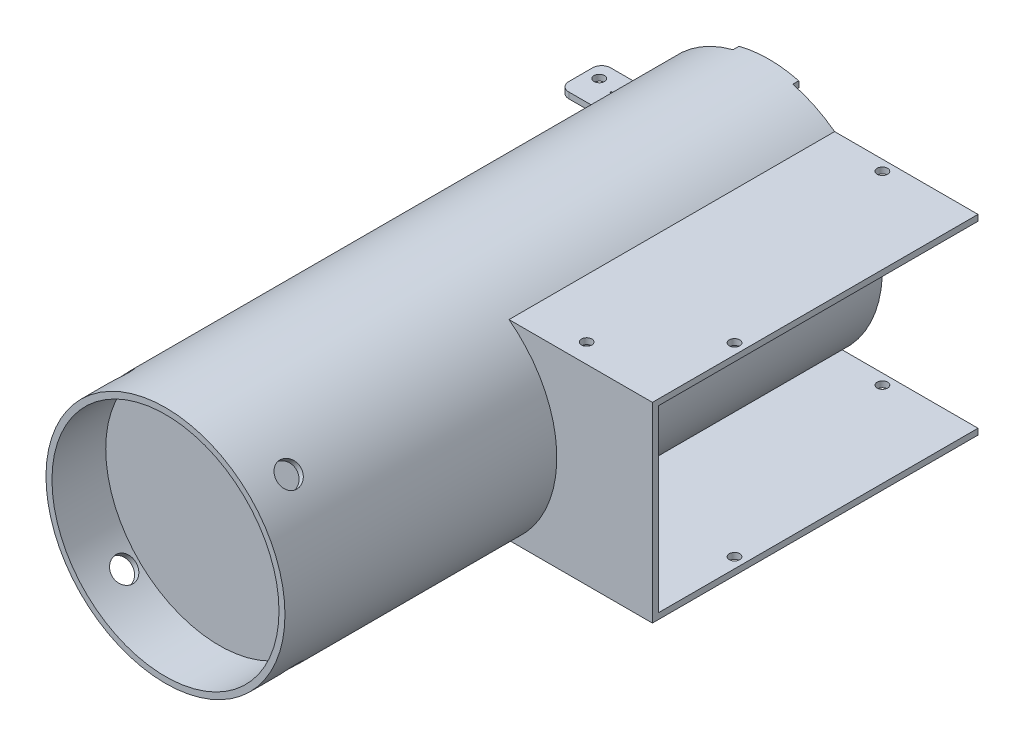
SolidWorks part; units mm, degrees
material "Acrylic (Medium-high impact)"
ref_plane "Front Plane" through (0, 0, 0) normal (0, 0, 1) x (1, 0, 0)
ref_plane "Top Plane" through (0, 0, 0) normal (0, 1, 0) x (1, 0, 0)
ref_plane "Right Plane" through (0, 0, 0) normal (1, 0, 0) x (0, 0, -1)
ref_axis "Axis1" through (0, 0, -12.1) along (0, 0, 1)
sketch "Sketch1" plane through (0, 0, 0) normal (0, 0, 1) x (1, 0, 0)
  circle A0 centre (0, 0) radius 38
  circle A1 centre (0, 0) radius 40
  dimension "D1" = 76
  dimension "D2" = 2
extrude "Boss-Extrude1" add sketch "Sketch1" along normal blind 200
ref_plane "Plane1" through (0, 0, 180) normal (0, 0, 1) x (1, 0, 0)
sketch "Sketch2" plane through (0, 0, 180) normal (0, 0, 1) x (1, 0, 0)
  circle A0 centre (0, 0) radius 40 construction
  circle A1 centre (0, 0) radius 40
extrude "Boss-Extrude2" add sketch "Sketch2" along normal blind 2
sketch "Sketch3" plane through (0, 0, 0) normal (0, 0, -1) x (-1, 0, 0)
  line L0 (-24, -32) -> (-72, -32)
  line L1 (-72, -32) -> (-72, -30)
  line L2 (-72, -30) -> (-26.4575, -30)
  line L3 (-24, 32) -> (-72, 32)
  line L4 (-72, 30) -> (-26.4575, 30)
  line L5 (-72, 32) -> (-72, 30)
  line L6 (-40, -15.2942) -> (-40, 13.2229) construction
  line L8 (0, 0) -> (-59.0266, 0) construction
  circle A1 centre (0, 0) radius 40 construction
  arc A2 (-24, 32) -> (-26.4575, 30) centre (0, 0) ccw
  arc A3 (-26.4575, -30) -> (-24, -32) centre (0, 0) ccw
  dimension "D1" = 60
  dimension "D2" = 2
  dimension "D3" = 32
extrude "Boss-Extrude3" add sketch "Sketch3" against normal blind 107
sketch "Sketch4" plane through (0, 0, 107) normal (0, 0, 1) x (1, 0, 0)
  line L2 (72, -32) -> (24, -32) construction
  line L3 (24, 32) -> (72, 32) construction
  line L4 (72, -32) -> (24, -32)
  line L5 (24, 32) -> (72, 32)
  line L6 (72, -32) -> (72, 32)
  circle A0 centre (0, 0) radius 40 construction
  arc A2 (24, -32) -> (24, 32) centre (0, 0) ccw
extrude "Boss-Extrude4" add sketch "Sketch4" along normal blind 2
sketch "Sketch5" plane through (0, 32, 0) normal (0, 1, 0) x (1, 0, 0)
  circle A5 centre (43.5, -102.5) radius 1.75 construction
  circle A6 centre (43.5, -102.5) radius 1.75
  circle A7 centre (43.5, -3.5) radius 1.75 construction
  circle A8 centre (43.5, -3.5) radius 1.75
  circle A9 centre (68.5, -78) radius 1.75 construction
  circle A10 centre (68.5, -78) radius 1.75
extrude "Cut-Extrude1" cut sketch "Sketch5" against normal through all
ref_plane "Plane2" through (0, 0, 0) normal (-0.7071, 0.7071, 0) x (0, 0, 1)
sketch "Sketch6" plane through (0, 0, 0) normal (-0.7071, 0.7071, 0) x (0, 0, 1)
  line L0 (200, -40) -> (200, 40) construction
  line L1 (200, -40) -> (200, 40) construction
  circle A0 centre (187, 0) radius 4
  dimension "D1" = 8
  dimension "D2" = 13
extrude "Cut-Extrude2" cut sketch "Sketch6" against normal up to next and the other way up to next
pattern_circular "CirPattern1" count 2 every 90 about axis through (0, 0, -12.1) along (0, 0, 1) of "Cut-Extrude2"
ref_plane "Plane3" through (-54, 0, 0) normal (1, 0, 0) x (0, 0, -1)
sketch "Sketch7" plane through (-54, 0, 0) normal (1, 0, 0) x (0, 0, -1)
  line L0 (0, 0) -> (-33.0452, 0) construction
  line L1 (-14, -11) -> (0, -11)
  line L2 (-14, -11) -> (-14, -13)
  line L3 (-14, -13) -> (0, -13)
  line L4 (0, -11) -> (0, -13)
  line L5 (0, -40) -> (0, 40) construction
  line L6 (0, 11) -> (0, 13)
  line L7 (-14, 13) -> (0, 13)
  line L8 (-14, 11) -> (-14, 13)
  line L9 (-14, 11) -> (0, 11)
  dimension "D1" = 2
  dimension "D2" = 14
  dimension "D3" = 22
extrude "Boss-Extrude5" add sketch "Sketch7" along normal up to surface (15.5422 mm away) up to face at (25.3934, 30.9059, 187.8976)
sketch "Sketch8" plane through (0, -13, 0) normal (0, -1, 0) x (1, 0, 0)
  line L6 (-37.8286, 14) -> (-37.8286, 0) construction
  line L7 (-37.8286, 0) -> (-54, 0) construction
  circle A0 centre (-49.7703, 5.0088) radius 1.75
  dimension "D3" = 3.5
  dimension "D1" = 11.9417
  dimension "D2" = 5.0088
extrude "Cut-Extrude3" cut sketch "Sketch8" against normal up to surface (26 mm away) up to face at (-45.9143, 13, 7)
fillet "Fillet1" radius 3 4 edges at (-54, 12, 0) (-54, -12, 0) (-54, -12, 14) (-54, 12, 14)
sketch "Sketch9" plane through (0, 11, 0) normal (0, -1, 0) x (1, 0, 0)
  circle A0 centre (-43.7703, 7.0088) radius 0.25
  circle A1 centre (-49.7703, 5.0088) radius 1.75 construction
  dimension "D1" = 6
  dimension "D2" = 2
  dimension "D3" = 0.5
extrude "Cut-Extrude4" cut sketch "Sketch9" against normal up to next
sketch "Sketch10" plane through (0, 0, 0) normal (0, 0, -1) x (-1, 0, 0)
  line L0 (-10, 38.7298) -> (-10, 36.6606)
  line L2 (10, 38.7298) -> (10, 36.6606)
  line L3 (-10, -36.6606) -> (-10, -38.7298)
  line L4 (10, -36.6606) -> (10, -38.7298)
  line L5 (-10, 36.6606) -> (10, 36.6606) construction
  line L6 (0, 36.6606) -> (0, 0) construction
  circle A0 centre (0, 0) radius 38 construction
  arc A1 (37.8286, 13) -> (-24, 32) centre (0, 0) ccw construction
  arc A2 (-10, -36.6606) -> (10, -36.6606) centre (0, 0) ccw
  arc A3 (37.8286, 13) -> (-10, 38.7298) centre (0, 0) ccw
  arc A4 (10, 36.6606) -> (-10, 36.6606) centre (0, 0) ccw
  arc A5 (-24, -32) -> (37.8286, -13) centre (0, 0) ccw construction
  arc A6 (-10, -38.7298) -> (37.8286, -13) centre (0, 0) ccw
  arc M9 (37.8286, 13) -> (-24, 32) centre (0, 0) ccw
  arc M17 (-24, -32) -> (37.8286, -13) centre (0, 0) ccw
  circle M22 centre (0, 0) radius 38
  dimension "D1" = 20
extrude "Boss-Extrude6" add sketch "Sketch10" along normal blind 2 contours L4 L3 M22 M17 | L2 L0 M9 M22 region at (0, 38.5641, 0) region at (0, -38.5641, 0)
